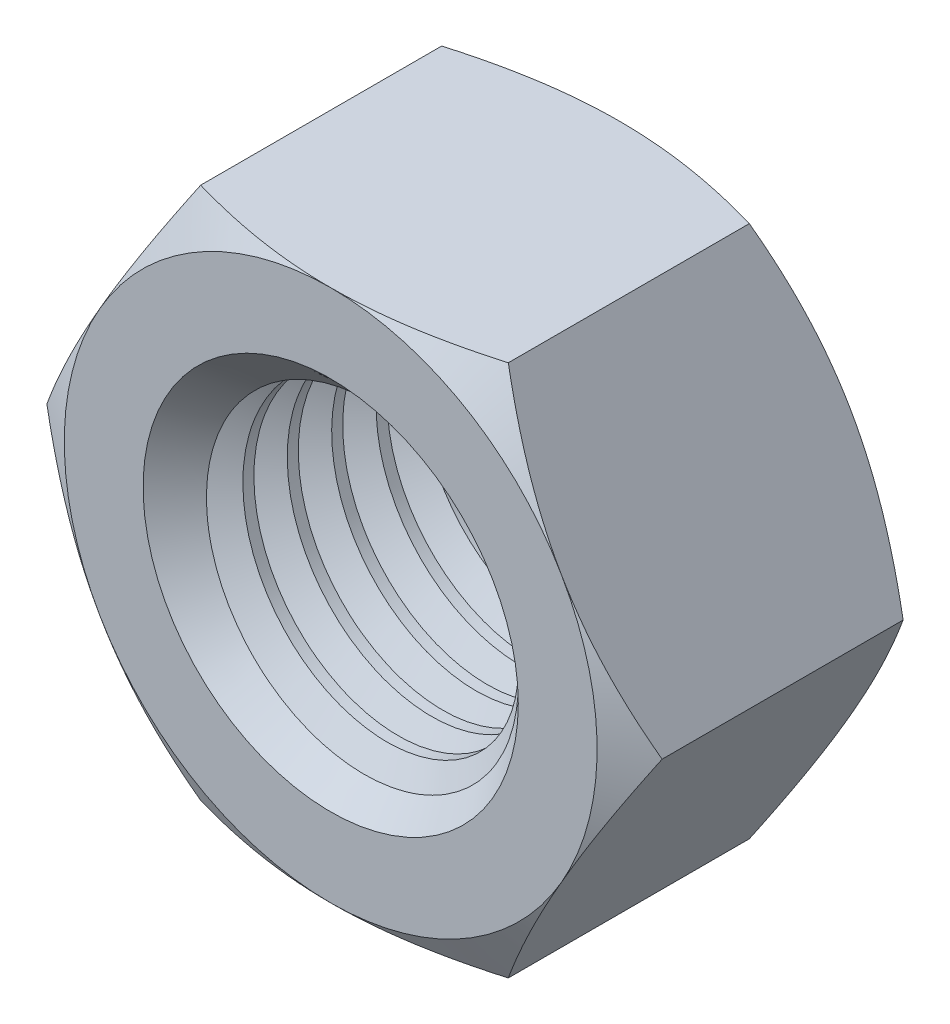
SolidWorks part; units mm, degrees
ref_plane "Front" through (0, 0, 0) normal (0, 0, 1) x (1, 0, 0)
ref_plane "Top" through (0, 0, 0) normal (0, 1, 0) x (1, 0, 0)
ref_plane "Right" through (0, 0, 0) normal (1, 0, 0) x (0, 0, -1)
sketch "Çizim1" plane through (0, 0, 0) normal (0, 0, 1) x (1, 0, 0)
  line L1 (13.8564, 0) -> (6.9282, 12)
  line L2 (6.9282, 12) -> (-6.9282, 12)
  line L3 (-6.9282, 12) -> (-13.8564, 0)
  line L4 (-13.8564, 0) -> (-6.9282, -12)
  line L5 (-6.9282, -12) -> (6.9282, -12)
  line L6 (6.9282, -12) -> (13.8564, 0)
  circle A0 centre (0, 0) radius 12 construction
  dimension "D1" = 24
extrude "Yükseklik-Ekstrüzyon1" add sketch "Çizim1" along normal blind 13
sketch "Çizim2" plane through (0, 0, 13) normal (0, 0, 1) x (1, 0, 0)
  circle A0 centre (0, 0) radius 12
extrude "Kes-Ekstrüzyon1" cut sketch "Çizim2" against normal blind 13 draft 60 flip side to cut
sketch "Çizim3" plane through (0, 0, 0) normal (0, 0, -1) x (-1, 0, 0)
  circle A0 centre (0, 0) radius 12
extrude "Kes-Ekstrüzyon2" cut sketch "Çizim3" against normal blind 13 draft 60 flip side to cut
sketch "Çizim4" plane through (0, 0, 0) normal (0, 0, -1) x (-1, 0, 0)
  circle A0 centre (0, 0) radius 6.7
  dimension "D1" = 13.4
extrude "Kes-Ekstrüzyon3" cut sketch "Çizim4" against normal blind 13
chamfer "Pah1" distance 1.75 angle 45 2 edges at (-6.7, 0, 13) (-6.7, 0, 0)
sketch "Çizim5" plane through (0, 0, 0) normal (0, 0, -1) x (-1, 0, 0)
  circle A0 centre (0, 0) radius 6.7
  dimension "D1" = 13.4
curve "Helis/Spiral1" pitch 2 height 15 radius 6.7 centre (0, 0, 0) axis (0, 0, 1) start towards (1, 0, 0)
ref_plane "Düzlem1" through (-6.7, 0, 15) normal (0, -0.9989, 0.0475) x (-1, 0, 0)
sketch "Çizim6" plane through (-6.7, 0, 15) normal (0, -0.9989, 0.0475) x (-1, 0, 0)
  line L1 (1.3, 0) -> (-0.3685, 0.9633)
  line L3 (-0.3685, -0.9633) -> (1.3, 0)
  line L4 (-0.3685, -0.9633) -> (-0.3685, 0.9633)
  line L5 (-0.65, 1.1258) -> (-0.65, 0) [skipped]
  arc A0 (-0.4674, -0.4517) -> (-0.4674, 0.4517) centre (0, 0) ccw construction
  dimension "D1" = 1.3
sweep "Kes-Süpür1" cut profiles "Çizim6" path "Helis/Spiral1" align with end faces yes
